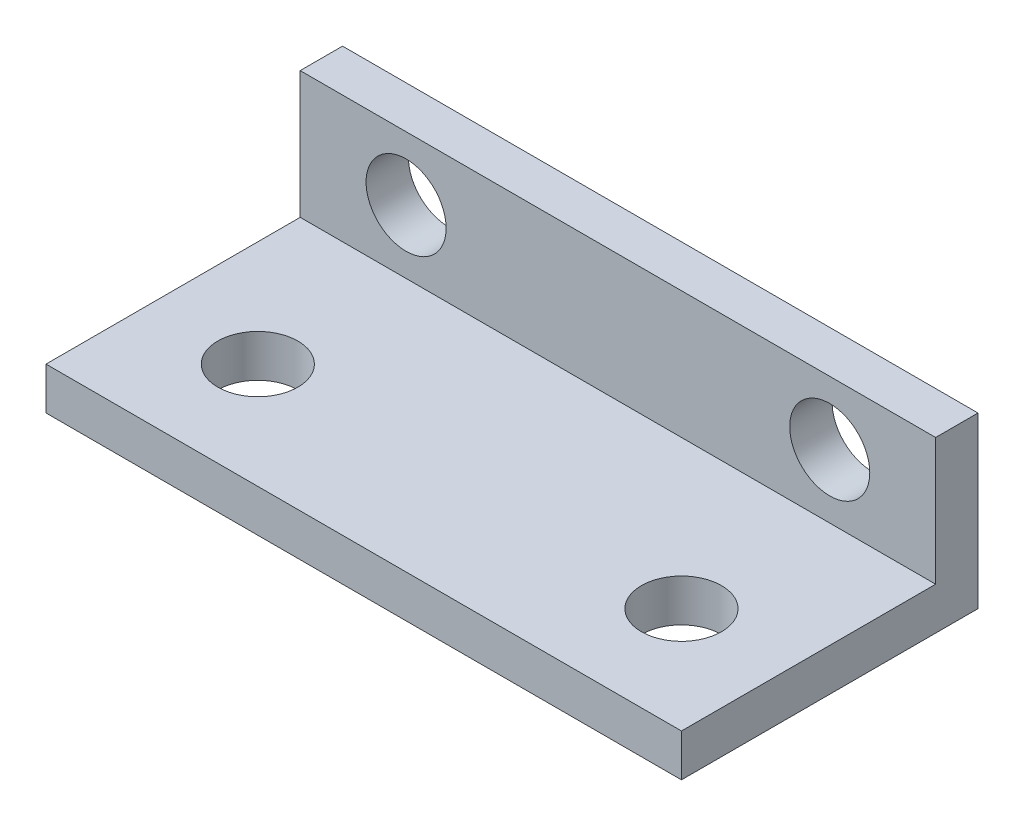
SolidWorks part; units mm, degrees
ref_plane "Front Plane" through (0, 0, 0) normal (0, 0, 1) x (1, 0, 0)
ref_plane "Top Plane" through (0, 0, 0) normal (0, 1, 0) x (1, 0, 0)
ref_plane "Right Plane" through (0, 0, 0) normal (1, 0, 0) x (0, 0, -1)
sketch "Sketch2" plane through (0, 0, 0) normal (1, 0, 0) x (0, 0, -1)
  line L1 (0, 0) -> (10.16, 0)
  line L2 (0, 0) -> (0, 10.16)
  line L3 (0, 10.16) -> (10.16, 10.16)
  line L4 (10.16, 0) -> (10.16, 10.16)
  line L5 (5.08, 10.16) -> (5.08, 0) construction
  line L6 (0, 5.08) -> (10.16, 5.08) construction
  point P204 (5.08, 5.08)
  dimension "D1" = 10.16
extrude "Boss-Extrude1" add sketch "Sketch2" along normal blind 38.1
sketch "Sketch3" plane through (38.1, 0, 0) normal (1, 0, 0) x (0, 0, -1)
  line L0 (10.16, 0) -> (10.16, 10.16) construction
  line L1 (0, 10.16) -> (7.62, 10.16)
  line L2 (0, 10.16) -> (0, 2.54)
  line L3 (0, 2.54) -> (7.62, 2.54)
  line L4 (7.62, 10.16) -> (7.62, 2.54)
  line L5 (3.81, 2.54) -> (3.81, 10.16) construction
  line L6 (0, 6.35) -> (7.62, 6.35) construction
  point P556 (3.81, 6.35)
  dimension "D1" = 2.54
extrude "Cut-Extrude1" cut sketch "Sketch3" against normal up to surface (38.1 mm away) and the other way through all up to face at (0, 5.08, -5.08)
sketch "Sketch7" plane through (0, 0, -7.62) normal (0, 0, 1) x (1, 0, 0)
  line L0 (0, 6.35) -> (38.1, 6.35) construction
  line L1 (0, 2.54) -> (0, 10.16) construction
  line L2 (38.1, 10.16) -> (38.1, 2.54) construction
  line L3 (38.1, 0) -> (0, 0) construction
  line L4 (6.35, 10.16) -> (6.35, 2.54) construction
  line L5 (0, 10.16) -> (38.1, 10.16) construction
  line L6 (0, 2.54) -> (38.1, 2.54) construction
  line L7 (19.05, 10.16) -> (19.05, 2.54) construction
  line L8 (31.75, 10.16) -> (31.75, 2.54) construction
  dimension "D1" = 6.35
  dimension "D2" = 6.35
hole_wizard "M4 Clearance Hole2" positions "Sketch10" profile "Sketch11" hole size "M4" standard "ANSI Metric" end condition through all
sketch "Sketch10" plane through (0, 0, -7.62) normal (0, 0, 1) x (1, 0, 0)
  line L0 (6.35, 10.16) -> (6.35, 2.54) construction
  line L1 (31.75, 10.16) -> (31.75, 2.54) construction
  point P0 (6.35, 6.35)
  point P4 (31.75, 6.35)
sketch "Sketch11" plane through (6.35, 6.35, -7.62) normal (1, 0, 0) x (0, -1, 0)
  line L0 (0, 0) -> (0, 2.54)
  line L1 (0, 2.54) -> (2.4, 2.54)
  line L2 (2.4, 2.54) -> (2.4, 0)
  line L5 (2.4, 0) -> (0, 0)
  line L11 (0, -6.35) -> (0, 107.95) construction
  dimension "Thru Hole Dia." = 4.8
  dimension "Thru Hole Depth" = 2.54
sketch "Sketch13" plane through (0, 0, 0) normal (0, 0, 1) x (1, 0, 0)
  line L1 (0, 2.54) -> (38.1, 2.54)
  line L2 (0, 2.54) -> (0, 0)
  line L3 (0, 0) -> (38.1, 0)
  line L4 (38.1, 2.54) -> (38.1, 0)
  line L5 (19.05, 0) -> (19.05, 2.54) construction
  line L6 (0, 1.27) -> (38.1, 1.27) construction
  point P300 (19.05, 1.27)
extrude "Boss-Extrude2" add sketch "Sketch13" along normal blind 7.62
sketch "Sketch14" plane through (0, 2.54, 0) normal (0, 1, 0) x (1, 0, 0)
  line L0 (0, -1.27) -> (38.1, -1.27) construction
  line L1 (0, 7.62) -> (38.1, 7.62) construction
  line L3 (0, -7.62) -> (0, 7.62) construction
  line L4 (38.1, 7.62) -> (38.1, -7.62) construction
  line L5 (38.1, -7.62) -> (0, -7.62) construction
  line L6 (6.35, 7.62) -> (6.35, -7.62) construction
  line L7 (31.75, 7.62) -> (31.75, -7.62) construction
  dimension "D1" = 6.35
hole_wizard "M4 Clearance Hole3" positions "Sketch15" profile "Sketch16" hole size "M4" standard "ANSI Metric" end condition through all
sketch "Sketch15" plane through (0, 2.54, 0) normal (0, 1, 0) x (1, 0, 0)
  line L0 (0, -1.27) -> (38.1, -1.27) construction
  line L1 (6.35, 7.62) -> (6.35, -7.62) construction
  line L2 (31.75, 7.62) -> (31.75, -7.62) construction
  point P0 (6.35, -1.27)
  point P6 (31.75, -1.27)
sketch "Sketch16" plane through (6.35, 2.54, 1.27) normal (1, 0, 0) x (0, 0, 1)
  line L0 (0, 0) -> (0, 2.54)
  line L1 (0, 2.54) -> (2.4, 2.54)
  line L2 (2.4, 2.54) -> (2.4, 0)
  line L5 (2.4, 0) -> (0, 0)
  line L11 (0, -6.35) -> (0, 107.95) construction
  dimension "Thru Hole Dia." = 4.8
  dimension "Thru Hole Depth" = 2.54
sketch "Sketch17" [suppressed] plane through (0, 0, -10.16) normal (0, 0, -1) x (-1, 0, 0)
  line L0 (-38.1, 0) -> (0, 0) construction
  line L1 (-38.1, 10.16) -> (-12.7, 10.16)
  line L2 (-38.1, 10.16) -> (-38.1, 0)
  line L3 (-38.1, 0) -> (-12.7, 0)
  line L4 (-12.7, 10.16) -> (-12.7, 0)
  line L5 (-25.4, 0) -> (-25.4, 10.16) construction
  line L6 (-38.1, 5.08) -> (-12.7, 5.08) construction
  circle A0 centre (-6.35, 6.35) radius 2.4 construction
  point P236 (-25.4, 5.08)
  dimension "D1" = 6.35
extrude "Cut-Extrude2" [suppressed] cut sketch "Sketch17" against normal up to surface (17.78 mm away) up to face at (19.05, 1.27, 7.62)
